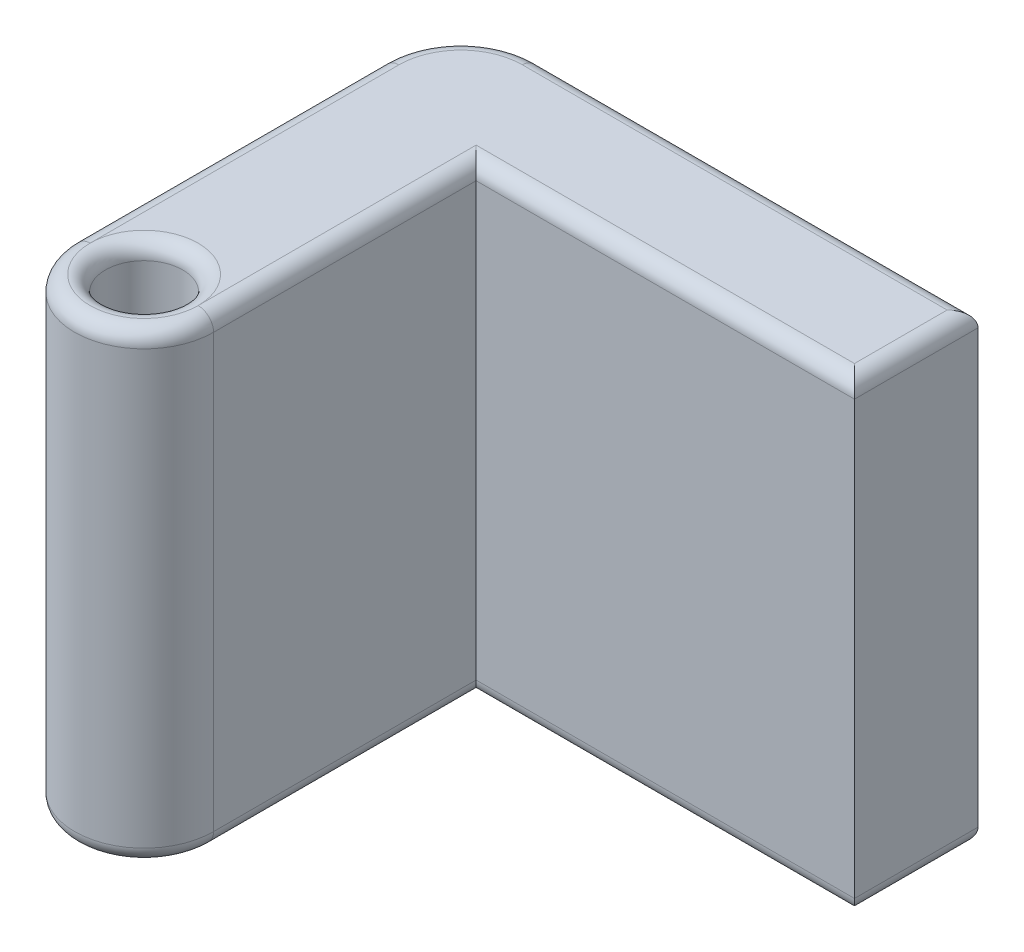
SolidWorks part; units mm, degrees
ref_plane "Front Plane" through (0, 0, 0) normal (0, 0, 1) x (1, 0, 0)
ref_plane "Top Plane" through (0, 0, 0) normal (0, 1, 0) x (1, 0, 0)
ref_plane "Right Plane" through (0, 0, 0) normal (1, 0, 0) x (0, 0, -1)
sketch "Sketch1" plane through (0, 0, 0) normal (0, 1, 0) x (1, 0, 0)
  line L0 (0, 0) -> (-33.5, 0)
  line L1 (-33.5, 0) -> (-33.5, -25)
  line L2 (-24.5, -25) -> (-24.5, -8)
  line L3 (-24.5, -8) -> (0, -8)
  line L4 (0, -8) -> (0, 0)
  arc A0 (-33.5, -25) -> (-24.5, -25) centre (-29, -25) ccw
  circle A1 centre (-29, -25) radius 2.5
  dimension "D2" = 5
  dimension "D1" = 24.5
  dimension "D3" = 9
  dimension "D4" = 8
  dimension "D5" = 17
extrude "Boss-Extrude1" add sketch "Sketch1" along normal blind 30
fillet "Fillet1" radius 1 14 edges at (-29, 0, 27.5) (-16.75, 0, 0) (-33.5, 0, 12.5) (-29, 0, 29.5) (-24.5, 0, 16.5) (-12.25, 0, 8) (0, 0, 4) (-29, 30, 27.5) (-12.25, 30, 8) (-24.5, 30, 16.5) (-29, 30, 29.5) (-33.5, 30, 12.5) (-16.75, 30, 0) (0, 30, 4)
fillet "Fillet2" radius 5 3 edges at (-33.2071, 0.2929, 0.2929) (-33.2071, 29.7071, 0.2929) (-33.5, 15, 0)
